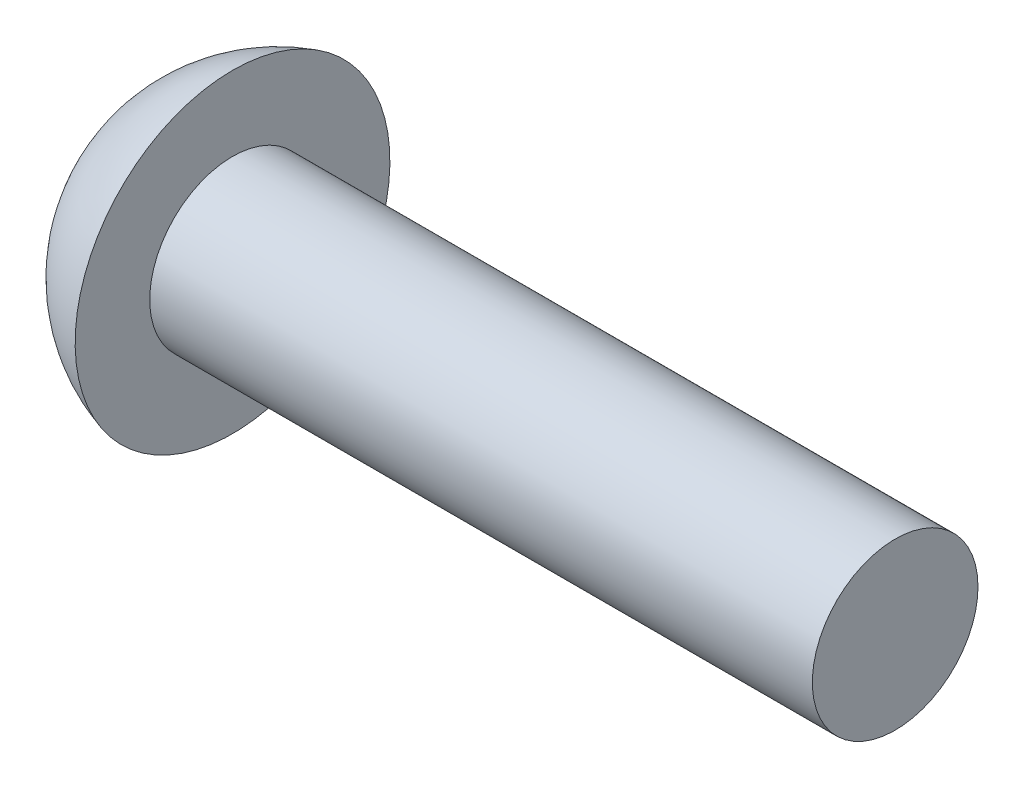
SolidWorks part; units mm, degrees
ref_plane "Front" through (0, 0, 0) normal (0, 0, 1) x (1, 0, 0)
ref_plane "Top" through (0, 0, 0) normal (0, 1, 0) x (1, 0, 0)
ref_plane "Right" through (0, 0, 0) normal (1, 0, 0) x (0, 0, -1)
sketch "Sketch1" plane through (0, 0, 0) normal (1, 0, 0) x (0, 0, -1)
  line L0 (0, 0) -> (1, 0) construction
  circle A0 centre (0, 0) radius 2.85
extrude "BaseHead" add sketch "Sketch1" along normal blind 1.65
sketch "Sketch2" plane through (1.65, 0, 0) normal (1, 0, 0) x (0, 0, -1)
  circle A0 centre (0, 0) radius 1.5
extrude "BaseBody" add sketch "Sketch2" along normal blind 12
cosmetic thread "ThreadCosmetic1" [suppressed] parameters "D1"=11, "THD_MINOR"=2.459
fillet "HeadFillet" [suppressed] radius 0.1
sketch "Sketch3" plane through (-13.4796, 2.4796, 0) normal (0, 0, 1) x (0, -1, 0)
  line L0 (2.4796, 13.4796) -> (2.4796, 41.0387) construction
  line L3 (-0.3704, 13.4796) -> (2.4796, 13.4796) construction
  line L5 (-5.3704, 15.1296) -> (-5.3704, 8.4796)
  line L6 (0.8296, 13.4796) -> (0.8296, 8.4796)
  line L7 (0.8296, 8.4796) -> (-5.3704, 8.4796)
  line L8 (-5.3704, 15.1296) -> (-0.3704, 15.1296)
  line L9 (-0.3704, 13.4796) -> (5.3296, 13.4796) construction
  arc A0 (-0.3704, 15.1296) -> (0.8296, 13.4796) centre (2.4796, 15.9409) ccw
  dimension "D2" = 5
  dimension "e" = 3.3
  dimension "D3" = 5
revolve "Cut-Revolve1" cut sketch "Sketch3" angle 360 about L0
sketch "Sketch4" plane through (0, 0, 0) normal (1, 0, 0) x (0, 0, -1)
  line L1 (1.1547, 0) -> (0.5774, 1)
  line L2 (0.5774, 1) -> (-0.5774, 1)
  line L3 (-0.5774, 1) -> (-1.1547, 0)
  line L4 (-1.1547, 0) -> (-0.5774, -1)
  line L5 (-0.5774, -1) -> (0.5774, -1)
  line L6 (0.5774, -1) -> (1.1547, 0)
  circle A0 centre (0, 0) radius 1 construction
  dimension "s" = 2
extrude "HexagonSocket" cut sketch "Sketch4" along normal blind 1.04
sketch "Sketch5" plane through (1.04, 0, 0) normal (-1, 0, 0) x (0, 0, 1)
  line L0 (0.5774, -1) -> (-0.5774, -1) construction
  line L1 (-0.5774, -1) -> (-1.1547, 0) construction
  line L2 (1.1547, 0) -> (0.5774, -1) construction
  line L3 (0.5774, 1) -> (1.1547, 0) construction
  line L4 (-1.1547, 0) -> (-0.5774, 1) construction
  line L5 (-0.5774, 1) -> (0.5774, 1) construction
  line L6 (0.5774, -1) -> (-0.5774, -1)
  line L7 (-0.5774, -1) -> (-1.1547, 0)
  line L8 (1.1547, 0) -> (0.5774, -1)
  line L9 (0.5774, 1) -> (1.1547, 0)
  line L10 (-1.1547, 0) -> (-0.5774, 1)
  line L11 (-0.5774, 1) -> (0.5774, 1)
extrude "Cut-Extrude2" cut sketch "Sketch5" against normal blind 5 draft 60
sketch "Sketch6" plane through (0, 0, 0) normal (0, 0, 1) x (1, 0, 0)
  line L0 (13.65, 1.2657) -> (13.7853, 1.5)
  line L1 (13.7853, 1.5) -> (13.7853, 1.7705)
  line L2 (13.7853, 1.7705) -> (13.5148, 1.7705)
  line L3 (13.5148, 1.7705) -> (13.5148, 1.5)
  line L4 (13.5148, 1.5) -> (13.65, 1.2657)
  line L5 (0, 0) -> (24.7294, 0) construction
  line L6 (13.65, -1.5) -> (13.65, 1.5) construction
  dimension "D1" = 0.2705
  dimension "D2" = 3
revolve "Cut-Revolve10" [suppressed] cut sketch "Sketch6" angle 360 about L5
pattern_linear "LPattern10" [suppressed] count 35 spacing 0.3246 along (-1, 0, 0) of bodies 106
equation "\"D1@ThreadCosmetic1\" = \"l@BaseBody\" - \"a@Sketch1\""
equation "\"D2@Sketch6\" = \"d@Sketch2\""
equation "\"D1@Sketch6\" =  (\"d@Sketch2\" - \"THD_MINOR@ThreadCosmetic1\" )  / 2"
equation "\"D3@LPattern10\" = \"D1@Sketch6\" * 1.2"
equation "\"D1@LPattern10\" = \"D1@ThreadCosmetic1\" / \"D3@LPattern10\" + 1"
